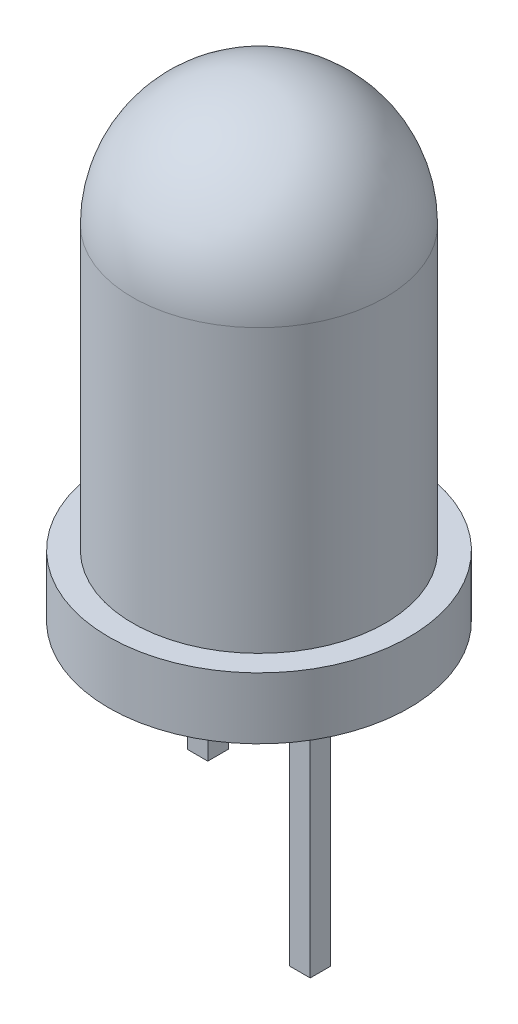
SolidWorks part; units mm, degrees
ref_plane "Front Plane" through (0, 0, 0) normal (0, 0, 1) x (1, 0, 0)
ref_plane "Top Plane" through (0, 0, 0) normal (0, 1, 0) x (1, 0, 0)
ref_plane "Right Plane" through (0, 0, 0) normal (1, 0, 0) x (0, 0, -1)
sketch "Sketch2" plane through (0, 0, 0) normal (0, 0, 1) x (1, 0, 0)
  line L0 (0, 0) -> (0, 8.7376) construction
  line L1 (0, 0) -> (2.794, 0)
  line L2 (2.794, 0) -> (2.794, 1.143)
  line L3 (2.794, 1.143) -> (2.3495, 1.143)
  line L4 (2.3495, 1.143) -> (2.3495, 6.3881)
  line L5 (0, 0) -> (0, 8.7376)
  arc A0 (2.3495, 6.3881) -> (0, 8.7376) centre (0, 6.3881) ccw
  dimension "D5" = 4.699
  dimension "D1" = 8.7376
  dimension "D2" = 5.588
  dimension "D3" = 1.143
  dimension "D4" = 4.699
revolve "Revolve1" add sketch "Sketch2" angle 360 about L0
sketch "Sketch3" plane through (0, 0, 0) normal (0, -1, 0) x (1, 0, 0)
  line L0 (0, 0) -> (0, 2.794) construction
  line L1 (-1.143, 0.1905) -> (-0.762, 0.1905)
  line L2 (-1.143, 0.1905) -> (-1.143, -0.1905)
  line L3 (-1.143, -0.1905) -> (-0.762, -0.1905)
  line L4 (-0.762, 0.1905) -> (-0.762, -0.1905)
  line L5 (-1.143, 0.1905) -> (-0.762, -0.1905) construction
  line L6 (-1.143, -0.1905) -> (-0.762, 0.1905) construction
  line L7 (0.762, 0.1905) -> (1.143, 0.1905)
  line L8 (0.762, 0.1905) -> (0.762, -0.1905)
  line L9 (0.762, -0.1905) -> (1.143, -0.1905)
  line L10 (1.143, 0.1905) -> (1.143, -0.1905)
  line L11 (0.762, 0.1905) -> (1.143, -0.1905) construction
  line L12 (0.762, -0.1905) -> (1.143, 0.1905) construction
  circle A0 centre (0, 0) radius 2.794 construction
  point P0 (-0.9525, 0)
  point P5 (0.9525, 0)
  dimension "D1" = 0.381
  dimension "D2" = 0.381
  dimension "D3" = 1.905
extrude "Boss-Extrude1" add sketch "Sketch3" along normal blind 5.08 contours L10 L7 L8 L9 region at (0.9525, 0, 0)
extrude "Boss-Extrude2" add sketch "Sketch3<4>" along normal blind 2.54 contours L4 L1 L2 L3 region at (-0.9525, 0, 0)
sketch "Sketch3<4>" plane through (0, 0, 0) normal (0, -1, 0) x (1, 0, 0) same geometry as "Sketch3"
scale "Echelle1" scale about centroid uniform scaling yes scale factor 4
